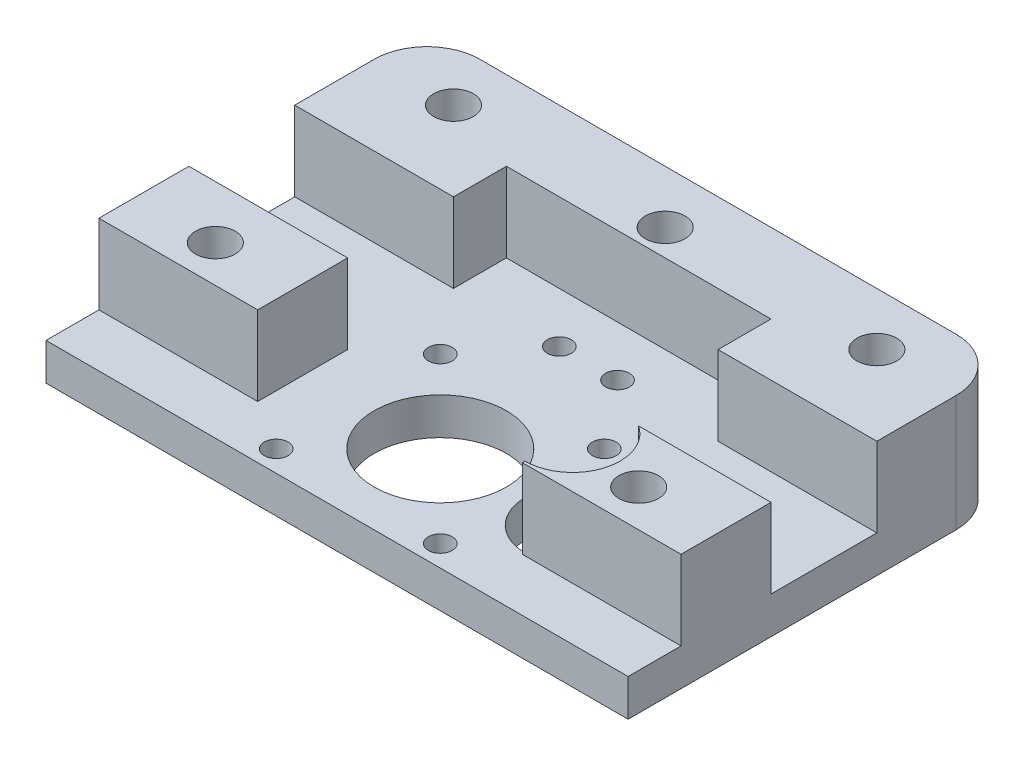
SolidWorks part; units mm, degrees
ref_plane "Front Plane" through (0, 0, 0) normal (0, 0, 1) x (1, 0, 0)
ref_plane "Top Plane" through (0, 0, 0) normal (0, 1, 0) x (1, 0, 0)
ref_plane "Right Plane" through (0, 0, 0) normal (1, 0, 0) x (0, 0, -1)
sketch "Sketch1" plane through (0, 0, 0) normal (0, 1, 0) x (1, 0, 0)
  line L0 (0, 0) -> (0, 36) construction
  line L1 (-55, 36) -> (55, 36)
  line L2 (-55, 36) -> (-55, -36)
  line L3 (-55, -36) -> (55, -36)
  line L4 (55, 36) -> (55, -36)
  line L5 (-55, 36) -> (55, -36) construction
  line L6 (-55, -36) -> (55, 36) construction
  line L15 (-15.5, -32) -> (15.5, -32) construction
  line L16 (-15.5, -32) -> (-15.5, -1) construction
  line L17 (-15.5, -1) -> (15.5, -1) construction
  line L18 (15.5, -32) -> (15.5, -1) construction
  line L19 (-15.5, -32) -> (15.5, -1) construction
  line L20 (-15.5, -1) -> (15.5, -32) construction
  circle A8 centre (0, -16.5) radius 12.5
  circle A9 centre (-15.5, -32) radius 2.25
  circle A10 centre (-15.5, -1) radius 2.25
  circle A11 centre (15.5, -1) radius 2.25
  circle A12 centre (15.5, -32) radius 2.25
  circle A13 centre (25, -16.5) radius 9
  circle A19 centre (-5.5, 11.5) radius 2.25
  circle A20 centre (5.5, 11.5) radius 2.25
  point P0 (0, 0)
  dimension "D2" = 25
  dimension "D4" = 16.5
  dimension "D5" = 4.5
  dimension "D6" = 18
  dimension "D7" = 25
  dimension "D15" = 4.5
  dimension "D1" = 110
  dimension "D3" = 31
  dimension "D8" = 72
  dimension "D14" = 24.5
  dimension "D16" = 5.5
  dimension "D17" = 11
extrude "Boss-Extrude1" add sketch "Sketch1" along normal blind 7
sketch "Sketch2" plane through (0, 7, 0) normal (0, 1, 0) x (1, 0, 0)
  line L1 (-55, 36) -> (55, 36)
  line L2 (-55, 36) -> (-55, -26)
  line L3 (-55, -26) -> (-25, -26)
  line L4 (-25, 21) -> (-25, -26)
  line L5 (-55, -36) -> (55, -36) construction
  line L6 (25, 21) -> (-25, 21)
  line L8 (55, 36) -> (55, -26)
  line L9 (55, -26) -> (25, -26)
  line L10 (25, 21) -> (25, -26)
  dimension "D1" = 30
  dimension "D4" = 15
  dimension "D5" = 10
extrude "Boss-Extrude2" add sketch "Sketch2" along normal blind 15
fillet "Fillet2" radius 10 2 edges at (55, 11, -36) (-55, 11, -36)
sketch "Sketch3" plane through (0, 0, 0) normal (0, -1, 0) x (1, 0, 0)
  line L0 (45, -36) -> (-45, -36) construction
  line L1 (55, 36) -> (55, -26) construction
  line L2 (-55, -26) -> (-55, 36) construction
  circle A0 centre (40, -26) radius 3.75
  circle A1 centre (-40, -26) radius 3.75
  circle A2 centre (-40, 19) radius 3.75
  circle A3 centre (0, -26) radius 3.75
  circle A4 centre (40, 19) radius 3.75
  dimension "D1" = 7.5
  dimension "D2" = 10
  dimension "D3" = 15
  dimension "D5" = 15
  dimension "D6" = 45
extrude "Cut-Extrude1" cut sketch "Sketch3" against normal through all
sketch "Sketch4" plane through (0, 22, 0) normal (0, 1, 0) x (1, 0, 0)
  line L0 (55, -26) -> (55, 26) construction
  line L1 (55, -9) -> (25, -9)
  line L2 (55, -9) -> (55, 11)
  line L3 (55, 11) -> (25, 11)
  line L4 (25, -9) -> (25, 11)
  line L5 (25, 21) -> (25, -26) construction
  line L6 (-25, -26) -> (-25, 21) construction
  line L7 (-25, -9) -> (-55, -9)
  line L8 (-25, -9) -> (-25, 11)
  line L9 (-25, 11) -> (-55, 11)
  line L10 (-55, -9) -> (-55, 11)
  line L11 (-55, 26) -> (-55, -26) construction
  line L12 (25, -26) -> (55, -26) construction
  dimension "D1" = 20
  dimension "D2" = 17
extrude "Cut-Extrude2" cut sketch "Sketch4" against normal up to surface (15 mm away) up to face at (4.1, 7, 16.7)
sketch "Sketch5" plane through (0, 7, 0) normal (0, -1, 0) x (1, 0, 0)
  line L2 (25, 25.5) -> (25, 9)
  line L3 (25, 9) -> (29.9749, 9)
  line L4 (25, 25.5) -> (25, 9)
  line L5 (25, 9) -> (29.9749, 9)
  arc A1 (29.9749, 9) -> (25, 25.5) centre (25, 16.5) ccw
  arc A2 (29.9749, 9) -> (25, 25.5) centre (25, 16.5) ccw
  dimension "D1" = 0
extrude "Cut-Extrude3" cut sketch "Sketch5" against normal through all
